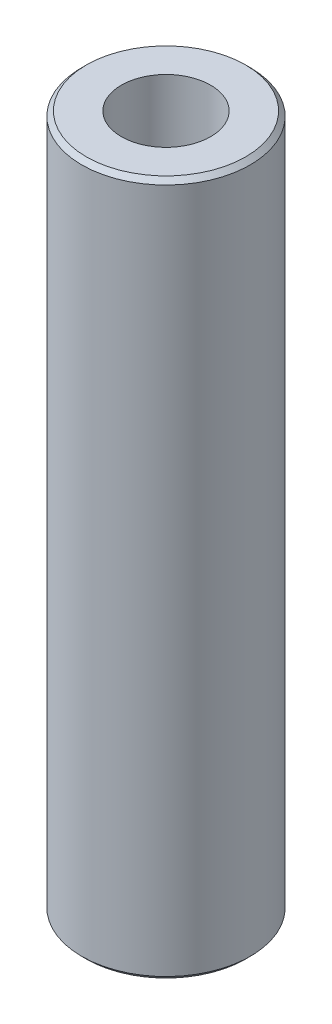
SolidWorks part; units mm, degrees
ref_plane "Front Plane" through (0, 0, 0) normal (0, 0, 1) x (1, 0, 0)
ref_plane "Top Plane" through (0, 0, 0) normal (0, 1, 0) x (1, 0, 0)
ref_plane "Right Plane" through (0, 0, 0) normal (1, 0, 0) x (0, 0, -1)
sketch "Sketch1" plane through (0, 0, 0) normal (0, 1, 0) x (1, 0, 0)
  circle A0 centre (0, 0) radius 30
  dimension "SHAFT_OD" = 60
extrude "Boss-Extrude1" add sketch "Sketch1" along normal blind 247.302
sketch "Sketch2" plane through (0, 0, 0) normal (0, 1, 0) x (1, 0, 0)
  circle A0 centre (0, 0) radius 15.9034
  dimension "BORE_D" = 31.8068
extrude "Cut-Extrude1" cut sketch "Sketch2" along normal through all
chamfer "Chamfer1" distance 1.6473 angle 45 2 edges at (0, 247.302, 30) (0, 0, 30)
